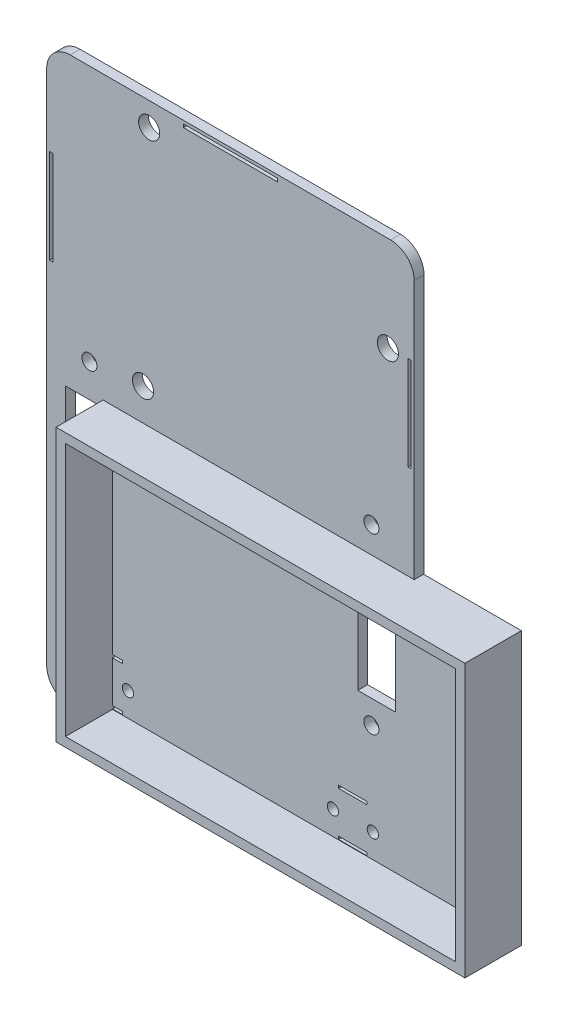
SolidWorks part; units mm, degrees
note: The reader was unsure of these and kept them because the rebuilt part matched: shared geometry of "Schizzo2<3>".
ref_plane "Front Plane" through (0, 0, 0) normal (0, 0, 1) x (1, 0, 0)
ref_plane "Top Plane" through (0, 0, 0) normal (0, 1, 0) x (1, 0, 0)
ref_plane "Right Plane" through (0, 0, 0) normal (1, 0, 0) x (0, 0, -1)
sketch "Sketch1" plane through (0, 0, 0) normal (0, 0, 1) x (1, 0, 0)
  line L0 (0, 60) -> (0, -60) construction
  line L1 (-39.1, -60) -> (39.1, -60)
  line L2 (-39.1, -60) -> (-39.1, 60)
  line L3 (-39.1, 60) -> (39.1, 60)
  line L4 (39.1, -60) -> (39.1, 60)
  line L5 (-39.1, -60) -> (39.1, 60) construction
  line L6 (-39.1, 60) -> (39.1, -60) construction
  line L7 (-18.6, 6.74) -> (33.5, 55) construction
  line L8 (-18.6, 56.235) -> (33.5, 6.74) construction
  circle A0 centre (-17.3, 55) radius 2.25
  circle A1 centre (33.5, 39.76) radius 2.25
  circle A3 centre (-18.6, 6.74) radius 2.25
  point P0 (0, 0)
  dimension "D8" = 4.5
  dimension "D1" = 78.2
  dimension "D2" = 120
  dimension "D4" = 50.8
  dimension "D5" = 48.26
  dimension "D6" = 1.3
  dimension "D7" = 15.24
  dimension "D9" = 5
  dimension "D10" = 21.8
extrude "Boss-Extrude1" add sketch "Sketch1" along normal blind 2.1
sketch "Sketch2" plane through (0, 0, 2.1) normal (0, 0, 1) x (1, 0, 0)
  line L0 (0, -60) -> (0, 0) construction
  line L1 (-39.1, -60) -> (39.1, -60) construction
  line L2 (-30.3, -51) -> (-21.8, -51) construction
  line L3 (-29.1, -46) -> (-23, -46)
  line L4 (-29.1, -46) -> (-29.1, -46.6)
  line L5 (-29.1, -46.6) -> (-23, -46.6)
  line L6 (-23, -46) -> (-23, -46.6)
  line L7 (-29.1, -46) -> (-23, -46.6) construction
  line L8 (-29.1, -46.6) -> (-23, -46) construction
  line L9 (-29.1, -55.4) -> (-23, -55.4)
  line L10 (-29.1, -55.4) -> (-29.1, -56)
  line L11 (-29.1, -56) -> (-23, -56)
  line L12 (-23, -55.4) -> (-23, -56)
  line L13 (-29.1, -55.4) -> (-23, -56) construction
  line L14 (-29.1, -56) -> (-23, -55.4) construction
  line L15 (-39.1, 60) -> (-39.1, -60) construction
  line L16 (29.1, -56) -> (23, -55.4) construction
  line L17 (29.1, -55.4) -> (23, -56) construction
  line L18 (29.1, -46.6) -> (23, -46) construction
  line L19 (29.1, -46) -> (23, -46.6) construction
  line L20 (30.3, -51) -> (21.8, -51) construction
  line L21 (23, -55.4) -> (23, -56)
  line L22 (29.1, -56) -> (23, -56)
  line L23 (29.1, -55.4) -> (29.1, -56)
  line L24 (29.1, -55.4) -> (23, -55.4)
  line L25 (23, -46) -> (23, -46.6)
  line L26 (29.1, -46.6) -> (23, -46.6)
  line L27 (29.1, -46) -> (29.1, -46.6)
  line L28 (29.1, -46) -> (23, -46)
  circle A0 centre (-30.3, -51) radius 1.2
  circle A1 centre (-21.8, -51) radius 1.2
  circle A2 centre (21.8, -51) radius 1.2
  circle A3 centre (30.3, -51) radius 1.2
  point P9 (-26.05, -46.3)
  point P14 (-26.05, -55.7)
  point P19 (-26.05, -51)
  point P36 (26.05, -55.7)
  point P37 (26.05, -46.3)
  dimension "D1" = 2.4
  dimension "D2" = 0.6
  dimension "D3" = 6.1
  dimension "D4" = 10
  dimension "D5" = 8.5
  dimension "D6" = 5
  dimension "D7" = 10
  dimension "D8" = 4
extrude "Cut-Extrude1" cut sketch "Sketch2" against normal up to next
sketch "Sketch3" plane through (0, 0, 2.1) normal (0, 0, 1) x (1, 0, 0)
  line L0 (39.1, -60) -> (39.1, 60) construction
  line L1 (-39.1, -60) -> (39.1, -60)
  line L2 (-39.1, -60) -> (-39.1, -44)
  line L3 (-39.1, -44) -> (39.1, -44)
  line L4 (39.1, -60) -> (39.1, -44)
  line L5 (-23, -46) -> (-29.1, -46) construction
  line L7 (-39.1, 60) -> (39.1, 60)
  line L8 (-39.1, 60) -> (-39.1, 2.74)
  line L9 (-39.1, 2.74) -> (39.1, 2.74)
  line L10 (39.1, 60) -> (39.1, 2.74)
  circle A0 centre (-18.6, 6.74) radius 2.25 construction
  dimension "D1" = 2
  dimension "D2" = 4
sketch "Sketch8" plane through (0, 0, 2.1) normal (0, 0, 1) x (1, 0, 0)
  line L0 (-39.1, 60) -> (-39.1, -60) construction
  line L1 (-35.1, -26.5) -> (-27.1, -26.5)
  line L2 (-35.1, -26.5) -> (-35.1, -1.5)
  line L3 (-35.1, -1.5) -> (-27.1, -1.5)
  line L4 (-27.1, -26.5) -> (-27.1, -1.5)
  line L5 (-35.1, -26.5) -> (-27.1, -1.5) construction
  line L6 (-35.1, -1.5) -> (-27.1, -26.5) construction
  line L7 (27.1, -26.5) -> (35.1, -26.5)
  line L8 (27.1, -26.5) -> (27.1, -1.5)
  line L9 (27.1, -1.5) -> (35.1, -1.5)
  line L10 (35.1, -26.5) -> (35.1, -1.5)
  line L11 (27.1, -26.5) -> (35.1, -1.5) construction
  line L12 (27.1, -1.5) -> (35.1, -26.5) construction
  line L13 (39.1, -60) -> (39.1, 60) construction
  line L15 (-39.1, -60) -> (39.1, -60) construction
  line L17 (-30, -31.5) -> (30, -31.5) construction
  line L18 (-39.1, -44) -> (39.1, -44) construction
  circle A0 centre (-30, -31.5) radius 1.6
  circle A1 centre (30, -31.5) radius 1.6
  circle A2 centre (30, 5.5) radius 1.6
  circle A3 centre (-30, 5.5) radius 1.6
  point P0 (-31.1, -14)
  point P5 (31.1, -14)
  point P13 (0, -31.5)
  point P29 (0, -44)
  dimension "D5" = 3.2
  dimension "D8" = 5
  dimension "D1" = 8
  dimension "D2" = 25
  dimension "D3" = 4
  dimension "D4" = 4
  dimension "D6" = 60
  dimension "D7" = 28.5
  dimension "D9" = 37
extrude "Cut-Extrude3" cut sketch "Sketch8" against normal up to next
fillet "Fillet2" radius 5 4 edges at (-39.1, 60, 1.05) (39.1, 60, 1.05) (39.1, -60, 1.05) (-39.1, -60, 1.05)
sketch "Schizzo2" plane through (0, 0, 2.1) normal (0, 0, 1) x (1, 0, 0)
  line L0 (-27.1, -26.5) -> (-27.1, -1.5) construction
  line L1 (-25.1, -2.1) -> (57.9, -2.1)
  line L2 (-25.1, -2.1) -> (-25.1, -56.1)
  line L3 (-25.1, -56.1) -> (57.9, -56.1)
  line L4 (57.9, -2.1) -> (57.9, -56.1)
  line L5 (-27.1, -0.1) -> (59.9, -0.1)
  line L6 (-27.1, -0.1) -> (-27.1, -58.1)
  line L7 (-27.1, -58.1) -> (59.9, -58.1)
  line L8 (59.9, -0.1) -> (59.9, -58.1)
  line L10 (-34.1, -60) -> (34.1, -60) construction
  circle M10 centre (30, -31.5) radius 1.6
  line M13 (35.1, -1.5) -> (35.1, -26.5)
  line M14 (35.1, -26.5) -> (27.1, -26.5)
  line M15 (27.1, -26.5) -> (27.1, -1.5)
  circle M21 centre (-21.8, -51) radius 1.2
  line M22 (-29.1, -46) -> (-23, -46)
  line M23 (-23, -46) -> (-23, -46.6)
  line M24 (-23, -46.6) -> (-29.1, -46.6)
  line M26 (-29.1, -55.4) -> (-23, -55.4)
  line M27 (-23, -55.4) -> (-23, -56)
  line M28 (-23, -56) -> (-29.1, -56)
  line M30 (23, -55.4) -> (29.1, -55.4)
  line M31 (29.1, -55.4) -> (29.1, -56)
  line M32 (29.1, -56) -> (23, -56)
  line M33 (23, -56) -> (23, -55.4)
  circle M34 centre (30.3, -51) radius 1.2
  circle M35 centre (21.8, -51) radius 1.2
  line M36 (23, -46) -> (29.1, -46)
  line M37 (29.1, -46) -> (29.1, -46.6)
  line M38 (29.1, -46.6) -> (23, -46.6)
  line M39 (23, -46.6) -> (23, -46)
  arc M46 (34.1, -60) -> (39.1, -55) centre (34.1, -55) ccw
  line M47 (39.1, -55) -> (39.1, 55)
  dimension "D1" = 83
  dimension "D2" = 54
  dimension "D3" = 0.1
  dimension "D4" = 2
  dimension "D5" = 2
  dimension "D6" = 2
  dimension "D7" = 2
extrude "Estrusione-Estrusione1" add sketch "Schizzo2" along normal blind 10
sketch "Schizzo3" plane through (0, 0, 2.1) normal (0, 0, 1) x (1, 0, 0)
  line L0 (34.1, 60) -> (-34.1, 60) construction
  line L1 (-38.45, 40) -> (-37.75, 40)
  line L2 (-38.45, 40) -> (-38.45, 20)
  line L3 (-38.45, 20) -> (-37.75, 20)
  line L4 (-37.75, 40) -> (-37.75, 20)
  line L5 (37.75, 40) -> (38.45, 40)
  line L6 (37.75, 40) -> (37.75, 20)
  line L7 (37.75, 20) -> (38.45, 20)
  line L8 (38.45, 40) -> (38.45, 20)
  line L9 (-10, 59.35) -> (10, 59.35)
  line L10 (-10, 59.35) -> (-10, 58.65)
  line L11 (-10, 58.65) -> (10, 58.65)
  line L12 (10, 59.35) -> (10, 58.65)
  line L13 (-39.1, 55) -> (-39.1, -55) construction
  line L14 (39.1, -55) -> (39.1, -2.1) construction
  line L15 (-34.1, -60) -> (34.1, -60) construction
  line L16 (-10, -59.3) -> (10, -59.3)
  line L17 (-10, -59.3) -> (-10, -58.65)
  line L18 (-10, -58.65) -> (10, -58.65)
  line L19 (10, -59.3) -> (10, -58.65)
  point P12 (0, 59.35)
  point P13 (-38.45, 30)
  point P15 (37.75, 30)
  point P28 (0, -59.3)
  dimension "D1" = 0.7
  dimension "D2" = 20
  dimension "D3" = 0.7
  dimension "D4" = 20
  dimension "D5" = 20
  dimension "D6" = 0.7
  dimension "D7" = 20
  dimension "D8" = 0.65
  dimension "D9" = 0.65
  dimension "D10" = 0.65
  dimension "D11" = 0.65
  dimension "D12" = 0.7
  dimension "D13" = 20
extrude "Taglio-Estrusione1" cut sketch "Schizzo3" against normal blind 1
extrude "Estrusione-Estrusione2" add sketch "Schizzo2<3>" against normal blind 2 contours L2 L3 L1 M46 M47 M13 M14 M15 M22 M23 M24 M26 M27 M28 M21 M35 M39 M36 M37 M38 M34 M33 M30 M31 M32 M10 | L4 L1 L3 M47 M46 | L6 L7 L8 L5
sketch "Schizzo2<3>" plane through (0, 0, 2.1) normal (0, 0, 1) x (1, 0, 0) same geometry as "Schizzo2"
